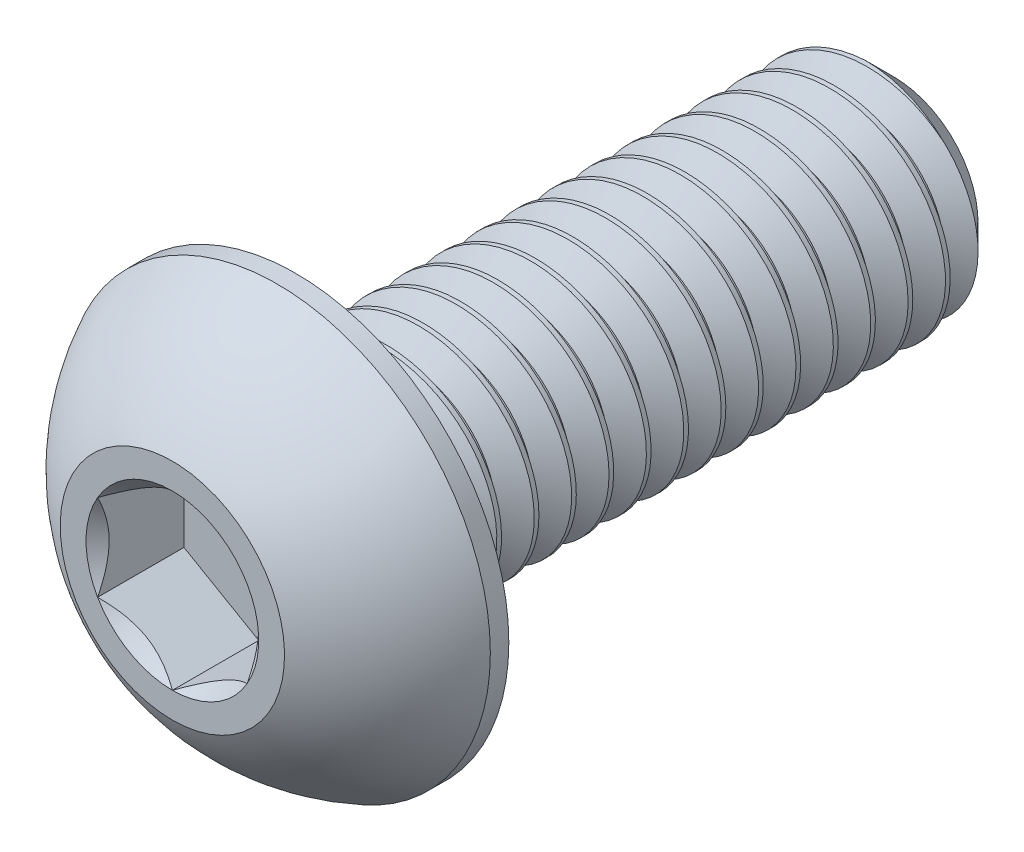
SolidWorks part; units mm, degrees
note: '?' marks a value the reader was unsure of.
ref_plane "Front" through (0, 0, 0) normal (0, 0, 1) x (1, 0, 0)
ref_plane "Top" through (0, 0, 0) normal (0, 1, 0) x (1, 0, 0)
ref_plane "Right" through (0, 0, 0) normal (1, 0, 0) x (0, 0, -1)
sketch "Sketch1" plane through (0, 0, 0) normal (1, 0, 0) x (0, 0, -1)
  line L2 (1.65, 1.5) -> (9.65, 1.5)
  line L3 (9.65, 1.5) -> (9.65, 0)
  line L4 (9.65, 0) -> (1.65, 0)
  line L6 (1.4025, 2.85) -> (1.65, 2.85) construction
  line L7 (9.65, 1.5) -> (9.65, -1.5) construction
  line L8 (0, 0) -> (1.65, 0) construction
  line L9 (1.65, 2.85) -> (1.65, -2.85) construction
  line L11 (1.65, 1.5) -> (1.65, 0)
  line L13 (0, 1) -> (0, -1) construction
  line L14 (0, 1) -> (0, 1.5) construction
  arc A3 (0, 1.5) -> (1.4025, 2.85) centre (2.7948, 0) cw construction
  dimension "D1" = 0.2475
  dimension "Head Ht" = 1.65
  dimension "Head Dia" = 5.7
  dimension "Dia" = 3
  dimension "Lg" = 8
  dimension "Hex" = 2
revolve "Revolve1" add sketch "Sketch1" angle 360 mid plane about L4
sketch "Sketch3" plane through (0, 0, -9.65) normal (0, 0, -1) x (-1, 0, 0)
  circle A0 centre (0, 0) radius 1.5
curve "Helix/Spiral1" pitch 0.5 height 8.5 turns 17
chamfer "Chamfer1" distance 0.375 angle 45 1 edges at (0, 1.5, -9.65)
sketch "Sketch7" plane through (0, 0, 0) normal (1, 0, 0) x (0, 0, -1)
  line L6 (1.4025, 2.85) -> (1.65, 2.85) construction
  line L8 (0, 0) -> (1.65, 0) construction
  line L11 (1.65, 2.85) -> (1.65, -2.85) construction
  line L12 (1.4025, 2.85) -> (1.65, 2.85)
  line L13 (0, 0) -> (1.65, 0)
  line L14 (0, 1) -> (0, -1) construction
  line L15 (1.65, 2.85) -> (1.65, 0)
  line L16 (0, 1.5) -> (0, 0)
  arc A2 (1.4025, 2.85) -> (0, 1.5) centre (2.7948, 0) ccw construction
  arc A3 (1.4025, 2.85) -> (0, 1.5) centre (2.7948, 0) ccw
revolve "Revolve2" add sketch "Sketch7" angle 360 mid plane about L13
sketch "Sketch5" plane through (0, 0, 0) normal (0, 0, 1) x (1, 0, 0)
  line L1 (1, -0.5774) -> (1, 0.5774)
  line L2 (1, 0.5774) -> (0, 1.1547)
  line L3 (0, 1.1547) -> (-1, 0.5774)
  line L4 (-1, 0.5774) -> (-1, -0.5774)
  line L5 (-1, -0.5774) -> (0, -1.1547)
  line L6 (0, -1.1547) -> (1, -0.5774)
  circle A0 centre (0, 0) radius 1 construction
extrude "Cut-Extrude2" cut sketch "Sketch5" against normal blind 1.155
sketch "Sketch6" plane through (0, 0, 0) normal (0, 0, 1) x (1, 0, 0)
  circle A0 centre (0, 0) radius 1.1547
extrude "Cut-Extrude3" cut sketch "Sketch6" against normal blind 1.155 draft 45
sketch "Sketch2" plane through (0, 0, 0) normal (1, 0, 0) x (0, 0, -1)
  line L0 (9.275, 1.5) -> (9.7125, 1.5)
  line L1 (9.7125, 1.5) -> (9.525, 1.1752)
  line L2 (9.525, 1.1752) -> (9.4625, 1.1752)
  line L3 (9.4625, 1.1752) -> (9.275, 1.5)
  line L4 (9.3687, 1.3376) -> (9.6187, 1.3376) construction
  dimension "D1" = 60
  dimension "D2" = 0.0625
  dimension "D3" = 0.25
sweep "Cut-Sweep1" cut profiles "Sketch2" path "Helix/Spiral1"
sketch "Sketch10" plane through (0, 0, 0) normal (1, 0, 0) x (0, 0, -1)
  line L0 (9.65, 1.5) -> (9.65, -1.5) construction
  point P0 (8.9, -1.5)
  dimension "D1" = 0.75
ref_axis "Center Axis 1" through (0, 0, -8.1113) along (0, 0, 1)?
ref_plane "Contact Plane 1" through (0, 0, -1.65) normal (0, 0, -1) x (-1, 0, 0)
ref_plane "Contact Plane 2" through (0, 0, 0) normal (0, 0, 1) x (1, 0, 0)
equation "\"D3@Helix/Spiral1\" = \"Lg@Sketch1\" + \"D4@Helix/Spiral1\""
equation "\"D2@Sketch2\" = \"D4@Helix/Spiral1\" * .125"
equation "\"D3@Sketch2\" = \"D4@Helix/Spiral1\" * .5"
equation "\"D1@Chamfer1\" = \"D4@Helix/Spiral1\" * .75"
equation "\"D1@Cut-Extrude2\" = \"Head Ht@Sketch1\" * .7"
equation "\"D1@Sketch1\" = \"Head Ht@Sketch1\" * .15"
equation "\"D1@Sketch10\" = \"D4@Helix/Spiral1\" * 1.5"
equation "\"D1@Cut-Extrude3\" = \"D1@Cut-Extrude2\""
